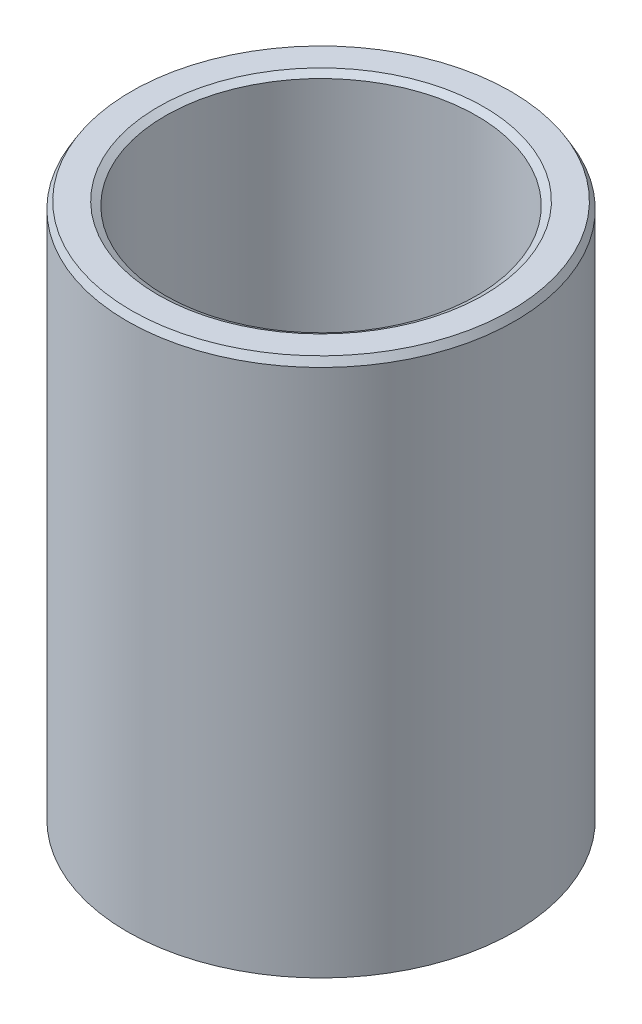
SolidWorks part; units mm, degrees
ref_plane "Front Plane" through (0, 0, 0) normal (0, 0, 1) x (1, 0, 0)
ref_plane "Top Plane" through (0, 0, 0) normal (0, 1, 0) x (1, 0, 0)
ref_plane "Right Plane" through (0, 0, 0) normal (1, 0, 0) x (0, 0, -1)
sketch "Sketch1" plane through (0, 0, 0) normal (0, 1, 0) x (1, 0, 0)
  circle A0 centre (0, 0) radius 27.5
  dimension "SLEEVE_OD" = 55
extrude "Boss-Extrude1" add sketch "Sketch1" along normal blind 76.5854
sketch "Sketch2" plane through (0, 0, 0) normal (0, 1, 0) x (1, 0, 0)
  circle A0 centre (0, 0) radius 22.0878
  dimension "BORE_D" = 44.1755
extrude "Cut-Extrude1" cut sketch "Sketch2" along normal through all
chamfer "Chamfer1" distance 1.0163 angle 30 4 edges at (0, 76.5854, 22.0878) (0, 0, 22.0878) (0, 0, 27.5) (0, 76.5854, 27.5) first distance on face at (0, 76.5854, 22.0878) first distance on face at (0, 0, 22.0878) first distance on face at (0, 76.5854, 27.5)
